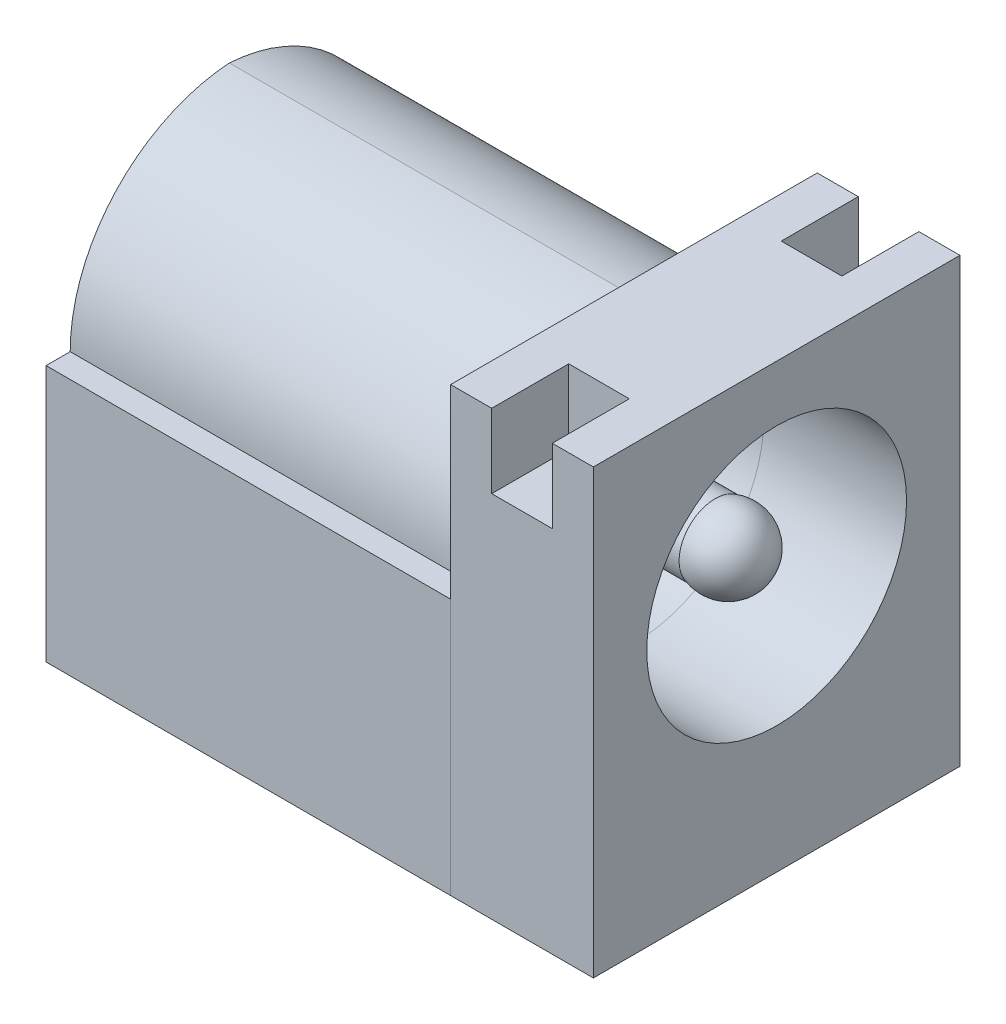
SolidWorks part; units mm, degrees
ref_plane "Front Plane" through (0, 0, 0) normal (0, 0, 1) x (1, 0, 0)
ref_plane "Top Plane" through (0, 0, 0) normal (0, 1, 0) x (1, 0, 0)
ref_plane "Right Plane" through (0, 0, 0) normal (1, 0, 0) x (0, 0, -1)
sketch "Sketch1" plane through (0, 0, 0) normal (1, 0, 0) x (0, 0, -1)
  line L1 (-4.5339, -5.4737) -> (4.5339, -5.4737)
  line L2 (-4.5339, -5.4737) -> (-4.5339, 5.4737)
  line L3 (-4.5339, 5.4737) -> (4.5339, 5.4737)
  line L4 (4.5339, -5.4737) -> (4.5339, 5.4737)
  line L5 (-4.5339, -5.4737) -> (4.5339, 5.4737) construction
  line L6 (-4.5339, 5.4737) -> (4.5339, -5.4737) construction
  point P0 (0, 0)
  dimension "D1" = 10.9474
  dimension "D2" = 9.0678
extrude "Extrude1" add sketch "Sketch1" against normal blind 3.5306
sketch "Sketch2" plane through (-3.5306, 0, 0) normal (-1, 0, 0) x (0, 0, 1)
  line L0 (-4.5339, -5.4737) -> (4.5339, -5.4737)
  line L1 (4.5339, -5.4737) -> (4.5339, 5.4737) construction
  line L2 (4.5339, 5.4737) -> (-4.5339, 5.4737) construction
  line L3 (-4.5339, 5.4737) -> (-4.5339, -5.4737) construction
  line L4 (0, -5.4737) -> (0, 5.0927) construction
  line L5 (-4.5339, -5.4737) -> (-4.5339, 0.8763)
  line L6 (4.5339, -5.4737) -> (4.5339, 0.8763)
  line L7 (-4.5339, 0.8763) -> (-3.937, 0.8763)
  line L8 (-3.937, 0.8763) -> (3.937, 0.8763) construction
  line L9 (3.937, 0.8763) -> (4.5339, 0.8763)
  arc A0 (-3.937, 0.8763) -> (0, 5.0927) centre (0.2893, 0.8763) cw
  arc A1 (3.937, 0.8763) -> (0, 5.0927) centre (-0.2893, 0.8763) ccw
  point P15 (0, 0.8763)
  dimension "D1" = 10.5664
  dimension "D2" = 7.874
extrude "Extrude2" add sketch "Sketch2" along normal blind 10.0076 separate body
sketch "Sketch3" plane through (0, 0, 0) normal (1, 0, 0) x (0, 0, -1)
  line L0 (3.937, 0.8763) -> (-3.937, 0.8763) construction
  circle A0 centre (0, 0.8763) radius 3.2131
  dimension "D1" = 6.4262
extrude "Extrude3" cut sketch "Sketch3" against normal blind 9.0678
sketch "Sketch4" plane through (-9.0678, 0, 0) normal (1, 0, 0) x (0, 0, -1)
  circle A0 centre (0, 0.8763) radius 0.889
extrude "Extrude4" add sketch "Sketch4" along normal blind 7.5438 separate body
dome "Dome1" faces to dome 1 distance 1.27 reverse direction no elliptical dome no face at (-1.524, 0.8763, -0.889) parameters "D1"=1.27
sketch "Sketch5" plane through (0, 5.4737, 0) normal (0, 1, 0) x (1, 0, 0)
  line L0 (-1.7653, 4.5339) -> (-1.7653, -4.5339) construction
  line L1 (-3.5306, 4.5339) -> (0, 4.5339) construction
  line L2 (-2.5146, -2.6289) -> (-1.016, -2.6289)
  line L3 (-2.5146, -2.6289) -> (-2.5146, -5.8039)
  line L4 (-2.5146, -5.8039) -> (-1.016, -5.8039)
  line L5 (-1.016, -2.6289) -> (-1.016, -5.8039)
  line L6 (-3.5306, -4.5339) -> (0, -4.5339) construction
  line L7 (0, 0) -> (-3.0951, 0) construction
  line L8 (-1.016, 2.6289) -> (-1.016, 5.8039)
  line L9 (-2.5146, 5.8039) -> (-1.016, 5.8039)
  line L10 (-2.5146, 2.6289) -> (-2.5146, 5.8039)
  line L11 (-2.5146, 2.6289) -> (-1.016, 2.6289)
  point P12 (-1.7653, -2.6289)
  dimension "D1" = 1.27
  dimension "D2" = 1.4986
  dimension "D3" = 1.905
extrude "Extrude5" cut sketch "Sketch5" against normal blind 1.8288
